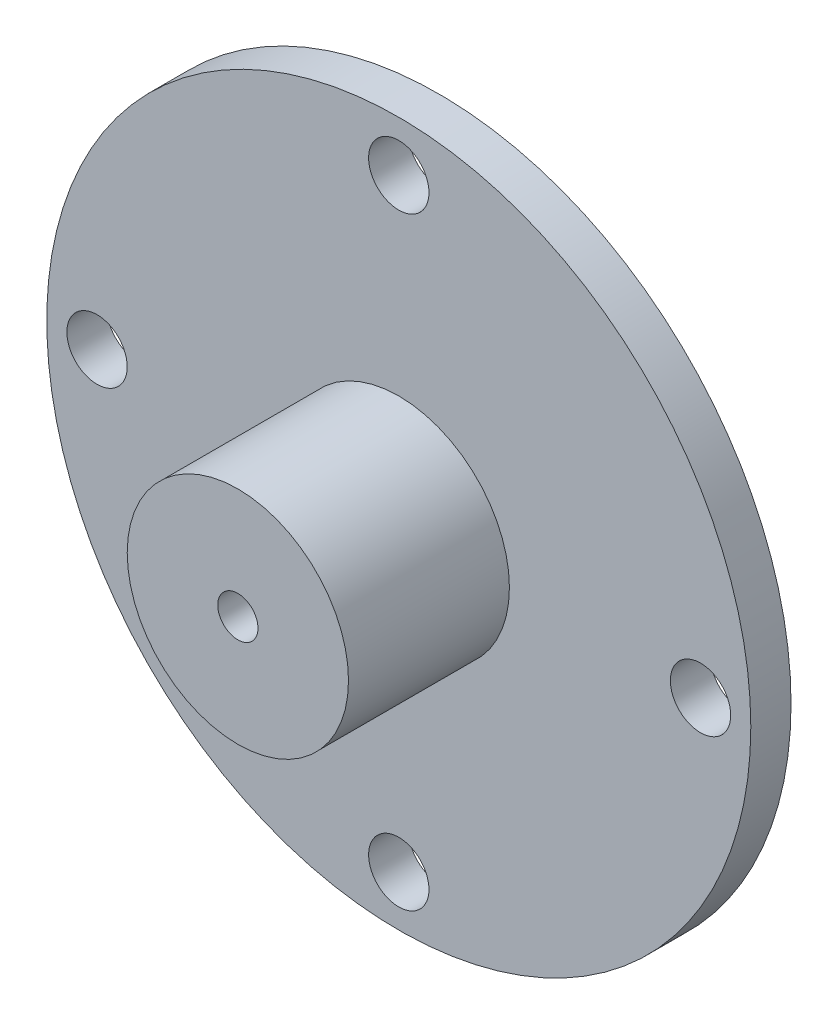
SolidWorks part; units mm, degrees
ref_plane "Front Plane" through (0, 0, 0) normal (0, 0, 1) x (1, 0, 0)
ref_plane "Top Plane" through (0, 0, 0) normal (0, 1, 0) x (1, 0, 0)
ref_plane "Right Plane" through (0, 0, 0) normal (1, 0, 0) x (0, 0, -1)
sketch "Sketch1" plane through (0, 0, 0) normal (0, 0, 1) x (1, 0, 0)
  circle A0 centre (0, 0) radius 15 construction
  circle A1 centre (0, 15) radius 1.5
  circle A2 centre (15, 0) radius 1.5
  circle A3 centre (0, -15) radius 1.5
  circle A4 centre (-15, 0) radius 1.5
  circle A5 centre (0, 0) radius 17.5
  circle A6 centre (0, 0) radius 5.5
  dimension "D1" = 30
  dimension "D2" = 3
  dimension "D3" = 35
  dimension "D4" = 11
extrude "Boss-Extrude1" add sketch "Sketch1" along normal blind 2 contours A5 A6 A1 A2 A3 A4 region at (-17.005, 0, 0)
extrude "Boss-Extrude3" add sketch "Sketch1<8>" along normal blind 10 contours A6 region at (0, 0, 0)
sketch "Sketch1<8>" plane through (0, 0, 0) normal (0, 0, 1) x (1, 0, 0) same geometry as "Sketch1"
sketch "Sketch6" plane through (0, 0, 10) normal (0, 0, 1) x (1, 0, 0)
  circle A0 centre (0, 0) radius 1
  dimension "D1" = 2
hole_wizard "Tap Drill for M2x0.4 Tap1" positions "Sketch7" profile "Sketch8" hole size "M2x0.4" standard "ANSI Metric"
sketch "Sketch7" plane through (0, 0, 10) normal (0, 0, 1) x (1, 0, 0)
  point P0 (0, 0)
sketch "Sketch8" plane through (0, 0, 10) normal (1, 0, 0) x (0, -1, 0)
  line L0 (0, 0) -> (0, 3.6009)
  line L1 (0, 3.6009) -> (1, 3)
  line L2 (1, 3) -> (1, 0)
  line L5 (1, 0) -> (0, 0)
  line L10 (0, 3.6009) -> (-1, 3) construction
  line L11 (0, -6.35) -> (0, 107.95) construction
  dimension "Hole Dia." = 2
  dimension "Hole Depth" = 3
  dimension "Drill Angle" = 118
